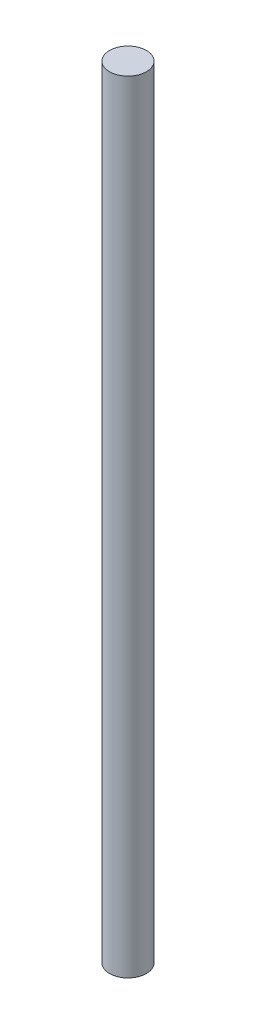
SolidWorks part; units mm, degrees
ref_plane "Front Plane" through (0, 0, 0) normal (0, 0, 1) x (1, 0, 0)
ref_plane "Top Plane" through (0, 0, 0) normal (0, 1, 0) x (1, 0, 0)
ref_plane "Right Plane" through (0, 0, 0) normal (1, 0, 0) x (0, 0, -1)
sketch "Sketch1" plane through (0, 0, 0) normal (0, 1, 0) x (1, 0, 0)
  circle A0 centre (0, 0) radius 6
extrude "Boss-Extrude1" add sketch "Sketch1" along normal blind 254
ref_axis "Midline" through (0, 254, 0) along (0, -1, 0)
